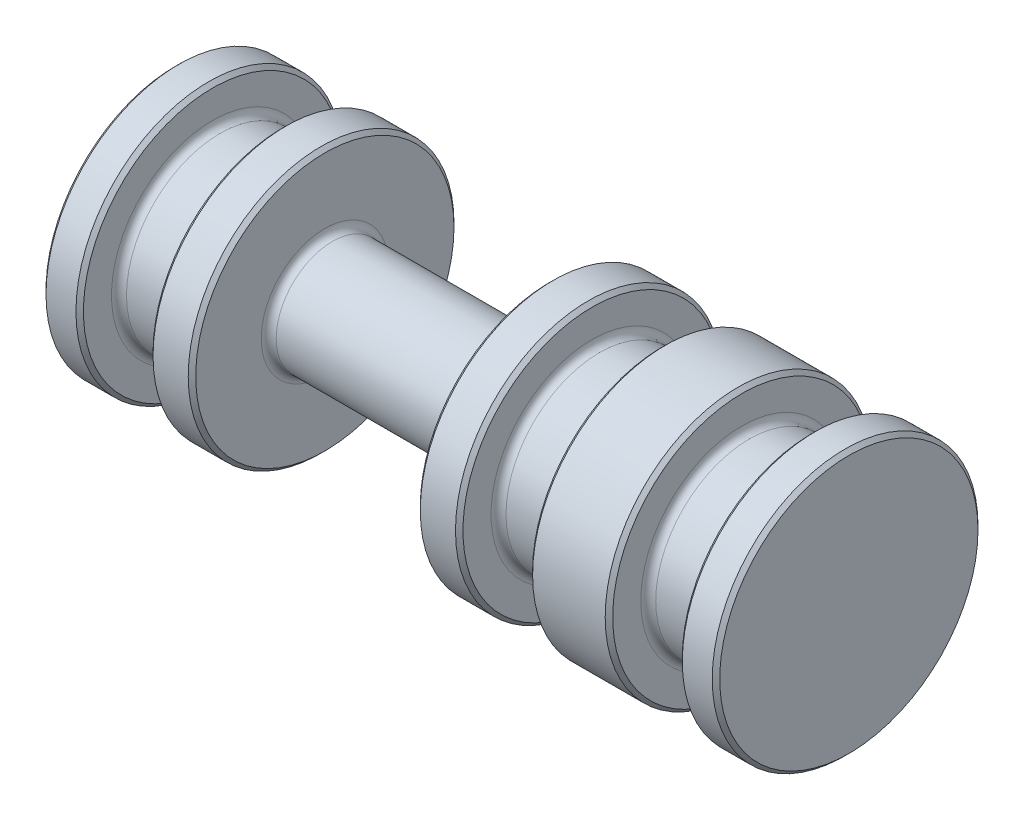
SolidWorks part; units mm, degrees
material "6063-T6"
ref_plane "Front Plane" through (0, 0, 0) normal (0, 0, 1) x (1, 0, 0)
ref_plane "Top Plane" through (0, 0, 0) normal (0, 1, 0) x (1, 0, 0)
ref_plane "Right Plane" through (0, 0, 0) normal (1, 0, 0) x (0, 0, -1)
sketch "Sketch1" plane through (0, 0, 0) normal (1, 0, 0) x (0, 0, -1)
  circle A0 centre (0, 0) radius 4.5085
  dimension "D1" = 9.017
extrude "Boss-Extrude1" add sketch "Sketch1" along normal blind 22.86
sketch "Sketch2" plane through (0, 0, 0) normal (0, 0, 1) x (1, 0, 0)
  line L0 (-1.6174, 0) -> (23.3579, 0) construction
  line L1 (1.27, 4.5085) -> (3.6322, 4.5085)
  line L2 (3.6322, 4.5085) -> (3.6322, 3.175)
  line L3 (3.6322, 3.175) -> (1.27, 3.175)
  line L4 (1.27, 3.175) -> (1.27, 4.5085)
  line L5 (0, 4.5085) -> (0, -4.5085) construction
  line L6 (17.78, 5.6982) -> (17.78, -5.5364) construction
  line L7 (22.86, -4.5085) -> (22.86, 4.5085) construction
  line L8 (19.2278, 4.5085) -> (21.59, 4.5085)
  line L9 (21.59, 4.5085) -> (21.59, 3.175)
  line L10 (21.59, 3.175) -> (19.2278, 3.175)
  line L11 (19.2278, 3.175) -> (19.2278, 4.5085)
  line L12 (14.1478, 4.5085) -> (16.51, 4.5085)
  line L13 (16.51, 4.5085) -> (16.51, 3.175)
  line L14 (16.51, 3.175) -> (14.1478, 3.175)
  line L15 (14.1478, 3.175) -> (14.1478, 4.5085)
  line L17 (5.08, 4.5085) -> (12.7, 4.5085)
  line L18 (5.08, 4.5085) -> (5.08, 1.905)
  line L19 (5.08, 1.905) -> (12.7, 1.905)
  line L20 (12.7, 4.5085) -> (12.7, 1.905)
  dimension "D1" = 9.017
  dimension "D2" = 6.35
  dimension "D3" = 2.3622
  dimension "D4" = 1.27
  dimension "D5" = 5.08
  dimension "D6" = 1.27
  dimension "D7" = 6.35
  dimension "D8" = 5.08
  dimension "D9" = 10.16
  dimension "D10" = 3.81
revolve "Cut-Revolve1" cut sketch "Sketch2" angle 360 about L0
fillet "Fillet1" radius 0.254 8 edges at (21.59, 0, 3.175) (19.2278, 0, 3.175) (16.51, 0, 3.175) (14.1478, 0, 3.175) (12.7, 0, 1.905) (5.08, 0, 1.905) (3.6322, 0, 3.175) (1.27, 0, 3.175)
chamfer "Chamfer1" distance 0.127 angle 45 5 edges at (12.7, 0, 4.5085) (0, 0, -4.5085) (21.59, 0, 4.5085) (16.51, 0, 4.5085) (3.6322, 0, 4.5085)
chamfer "Chamfer2" distance 0.127 angle 45 5 edges at (22.86, 0, -4.5085) (19.2278, 0, 4.5085) (14.1478, 0, 4.5085) (5.08, 0, 4.5085) (1.27, 0, 4.5085)
